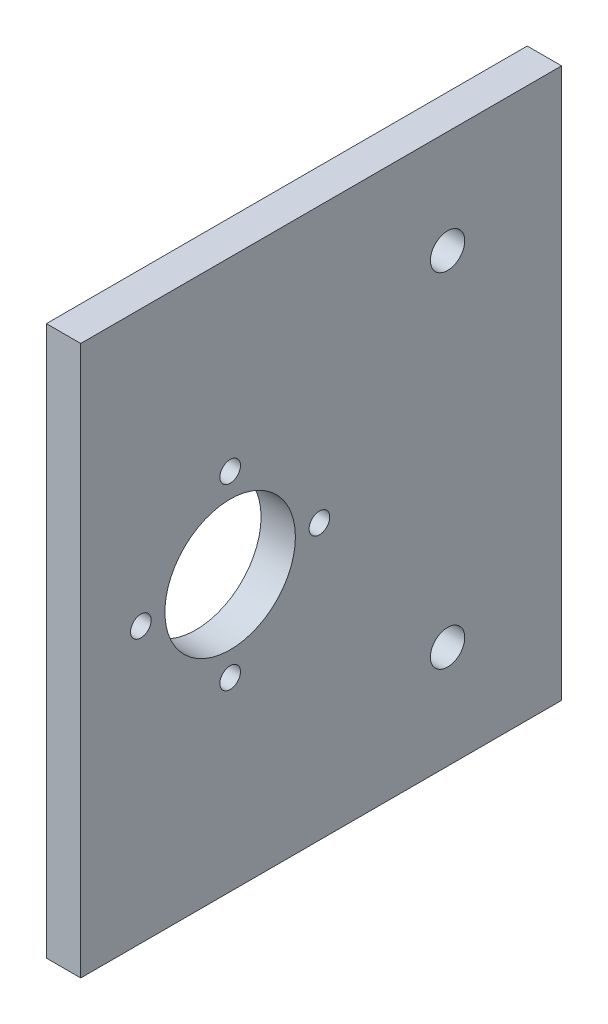
SolidWorks part; units mm, degrees
ref_plane "Front Plane" through (0, 0, 0) normal (1, 0, 0) x (0, 1, 0)
ref_plane "Top Plane" through (0, 0, 0) normal (0, 0, 1) x (0, 1, 0)
ref_plane "Right Plane" through (0, 0, 0) normal (0, 1, 0) x (-1, 0, 0)
sketch "Sketch1" plane through (0, 0, 0) normal (1, 0, 0) x (0, 1, 0)
  line L0 (-40, 13.25) -> (40, 13.25) construction
  line L1 (-40, -35) -> (40, -35)
  line L2 (-40, -35) -> (-40, 35)
  line L3 (-40, 35) -> (40, 35)
  line L4 (40, -35) -> (40, 35)
  line L5 (-40, -35) -> (40, 35) construction
  line L6 (-40, 35) -> (40, -35) construction
  line L7 (0, 35) -> (0, -35) construction
  line L8 (-40, -18.4) -> (40, -18.4) construction
  circle A1 centre (0, 26.25) radius 1.5
  circle A2 centre (0, 0.25) radius 1.5
  circle A3 centre (-13, 13.25) radius 1.5
  circle A4 centre (13, 13.25) radius 1.5
  circle A5 centre (0, 13.25) radius 9.5
  circle A6 centre (-25, -18.4) radius 2.5
  circle A7 centre (25, -18.4) radius 2.5
  point P0 (0, 0)
  dimension "D5" = 13
  dimension "D4" = 3
  dimension "D6" = 3
  dimension "D8" = 19
  dimension "D10" = 5
  dimension "D1" = 70
  dimension "D2" = 80
  dimension "D3" = 48.25
  dimension "D7" = 13
  dimension "D9" = 16.6
  dimension "D11" = 25
extrude "Boss-Extrude1" add sketch "Sketch1" along normal blind 5
